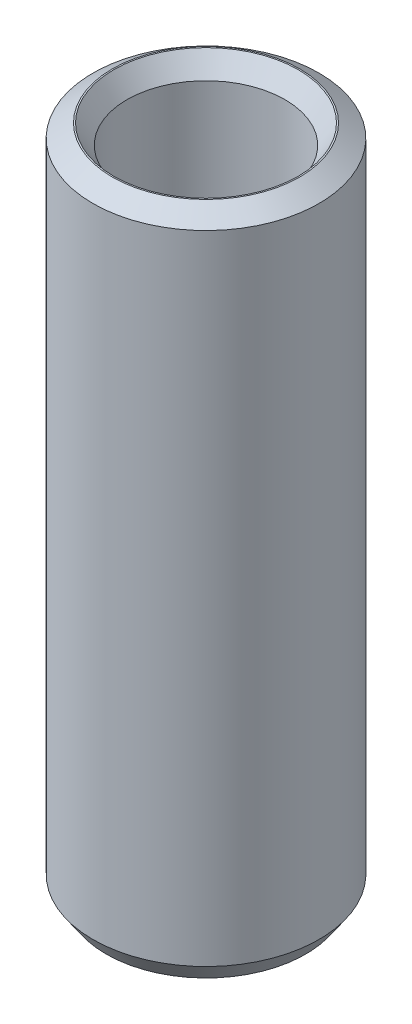
SolidWorks part; units mm, degrees
ref_plane "Front Plane" through (0, 0, 0) normal (0, 0, 1) x (1, 0, 0)
ref_plane "Top Plane" through (0, 0, 0) normal (0, 1, 0) x (1, 0, 0)
ref_plane "Right Plane" through (0, 0, 0) normal (1, 0, 0) x (0, 0, -1)
sketch "Sketch1" plane through (0, 0, 0) normal (0, 1, 0) x (1, 0, 0)
  circle A0 centre (0, 0) radius 10
  dimension "SLEEVE_OD" = 20
extrude "Boss-Extrude1" add sketch "Sketch1" along normal blind 59.2708
sketch "Sketch2" plane through (0, 0, 0) normal (0, 1, 0) x (1, 0, 0)
  circle A0 centre (0, 0) radius 6.9921
  dimension "BORE_D" = 13.9843
extrude "Cut-Extrude1" cut sketch "Sketch2" along normal through all
chamfer "Chamfer1" distance 1.1728 angle 55.524 4 edges at (0, 59.2708, 6.9921) (0, 0, 6.9921) (0, 0, 10) (0, 59.2708, 10) first distance on face at (0, 59.2708, 6.9921) first distance on face at (0, 0, 6.9921) first distance on face at (0, 59.2708, 10)
